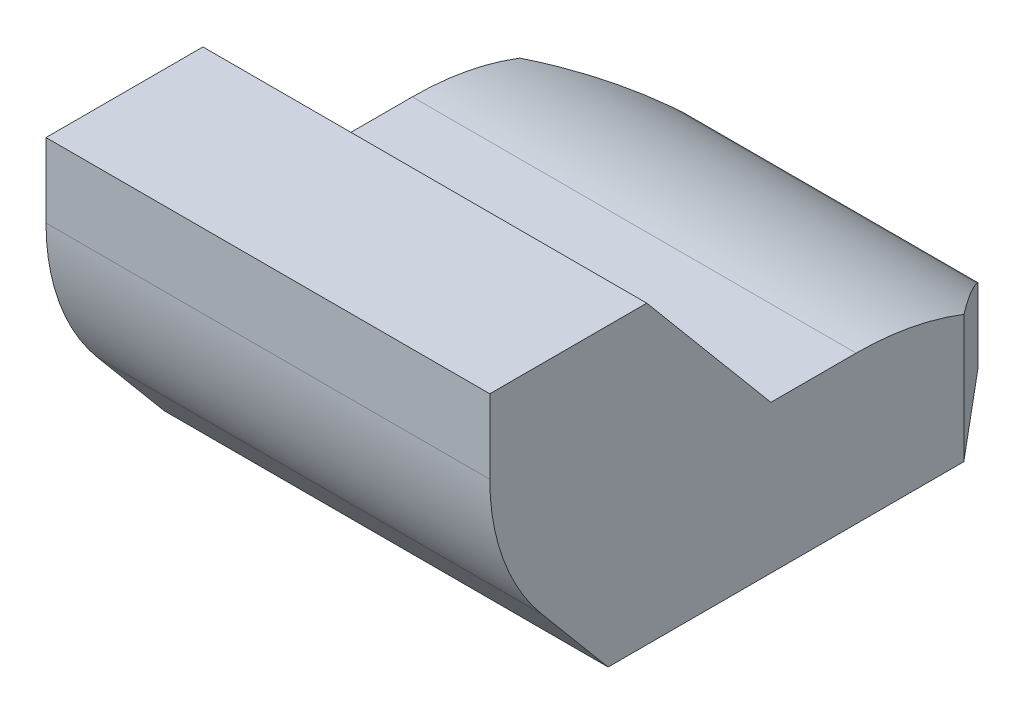
SolidWorks part; units mm, degrees
ref_plane "前视基准面" through (0, 0, 0) normal (0, 0, 1) x (1, 0, 0)
ref_plane "上视基准面" through (0, 0, 0) normal (0, 1, 0) x (1, 0, 0)
ref_plane "右视基准面" through (0, 0, 0) normal (1, 0, 0) x (0, 0, -1)
sketch "草图1" plane through (0, 0, 0) normal (0, 1, 0) x (1, 0, 0)
  line L5 (-1.5, 1) -> (1.5, 1)
  line L6 (-1.5, 1) -> (-1.5, -2.8)
  line L7 (-1.5, -2.8) -> (1.5, -2.8)
  line L8 (1.5, 1) -> (1.5, -2.8)
  point P4 (0, 1)
  dimension "D1" = 3
  dimension "D2" = 1
  dimension "D3" = 3.8
extrude "凸台-拉伸1" add sketch "草图1" along normal blind 1
sketch "草图2" plane through (0, 1, 0) normal (0, 1, 0) x (1, 0, 0)
  line L0 (1.5, -2.8) -> (1.5, 1) construction
  line L1 (-1.5, -2.8) -> (1.5, -2.8)
  line L2 (-1.5, -2.8) -> (-1.5, -1.8)
  line L3 (-1.5, -1.8) -> (1.5, -1.8)
  line L4 (1.5, -2.8) -> (1.5, -1.8)
  dimension "D1" = 1
extrude "凸台-拉伸2" add sketch "草图2" along normal blind 1
chamfer "倒角1" distance 0.5 angle 50 3 edges at (1.5, 0.5, -1) (-1.5, 0.5, -1) (0, 1, -1) first distance on face at (0, 0.5, -1)
fillet "圆角1" radius 2 1 edges at (0, 1, -0.4041)
chamfer "倒角4" distance 0.8 angle 50 1 edges at (0, 0, 2.8) first distance on face at (0, 0, 0.4653)
sketch "草图3" plane through (0, 0, 2.8) normal (0, 0, 1) x (1, 0, 0)
  line L0 (-0.75, 1) -> (0.75, 1) construction
  line L1 (-0.75, 2) -> (0.75, 2)
  line L2 (-0.75, 0) -> (0.75, 0)
  line L3 (-1.5, 2) -> (1.5, 2) construction
  line L4 (-1.5, 0) -> (1.5, 0) construction
  line L5 (0, 1) -> (0, 0) construction
  arc A0 (-0.75, 2) -> (-0.75, 0) centre (-0.75, 1) ccw
  arc A1 (0.75, 0) -> (0.75, 2) centre (0.75, 1) ccw
  point P2 (0, 1)
  dimension "D1" = 1.5
chamfer "倒角3" distance 0.9 angle 50 1 edges at (0, 1, 1.8) first distance on face at (0, 1, 1.0619)
fillet "圆角2" radius 1.5 1 edges at (0, 0.9534, 2.8)
